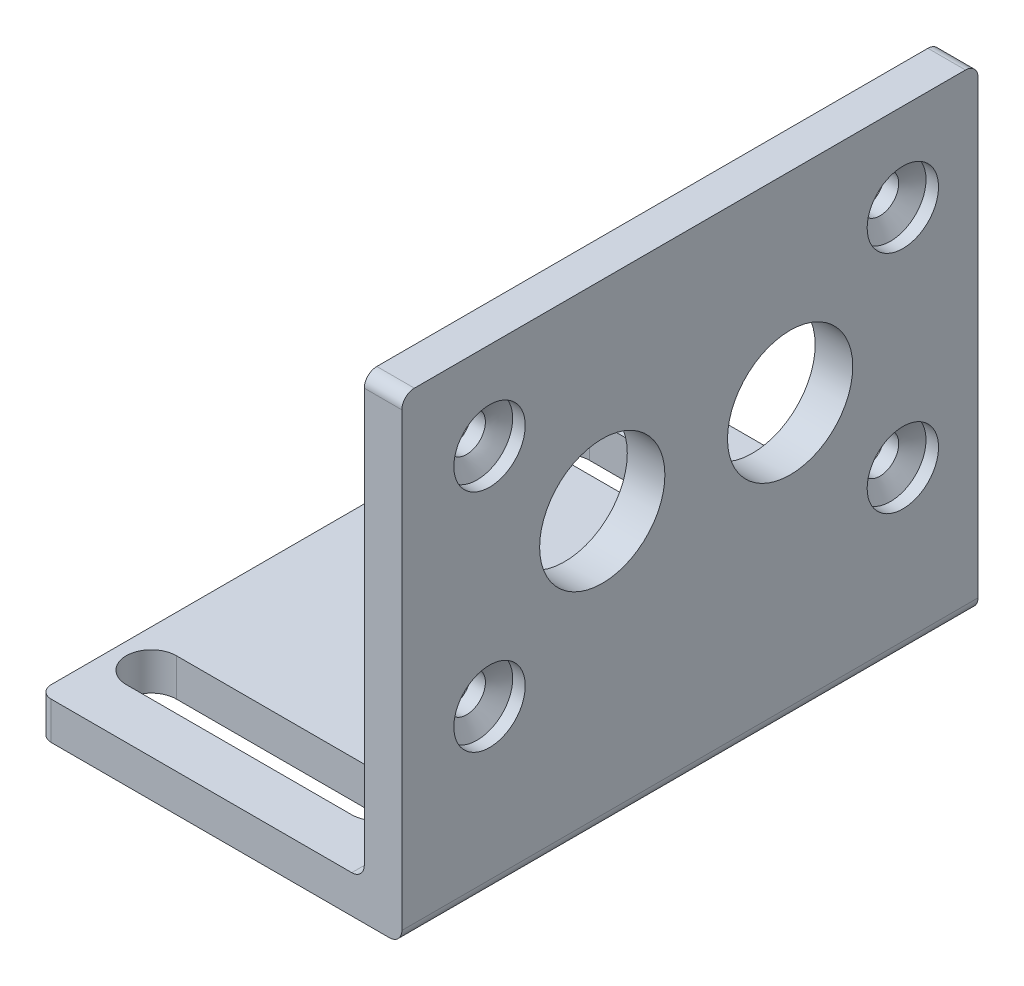
SolidWorks part; units mm, degrees
material "AISI 1020"
ref_plane "Alzado" through (0, 0, 0) normal (0, 0, 1) x (1, 0, 0)
ref_plane "Planta" through (0, 0, 0) normal (0, 1, 0) x (1, 0, 0)
ref_plane "Vista lateral" through (0, 0, 0) normal (1, 0, 0) x (0, 0, -1)
sketch "Croquis1" plane through (0, 0, 0) normal (0, 0, 1) x (1, 0, 0)
  line L0 (-36.9164, 3.6741) -> (-36.9164, -33.3259)
  line L1 (-37.9164, -34.3259) -> (-65.9164, -34.3259)
  line L2 (-65.9164, -34.3259) -> (-65.9164, -31.3259)
  line L3 (-65.9164, -31.3259) -> (-40.9164, -31.3259)
  line L4 (-39.9164, -30.3259) -> (-39.9164, 3.6741)
  line L5 (-39.9164, 3.6741) -> (-36.9164, 3.6741)
  arc A0 (-40.9164, -31.3259) -> (-39.9164, -30.3259) centre (-40.9164, -30.3259) ccw
  arc A1 (-36.9164, -33.3259) -> (-37.9164, -34.3259) centre (-37.9164, -33.3259) cw
  point P10 (-36.9164, -34.3259)
  dimension "D5" = 1
  dimension "D1" = 3
  dimension "D2" = 38
  dimension "D3" = 29
  dimension "D4" = 3
extrude "Saliente-Extruir1" add sketch "Croquis1" along normal blind 46
fillet "Redondeo1" radius 1 4 edges at (-38.4164, 3.6741, 0) (-65.9164, -32.8259, 0) (-65.9164, -32.8259, 46) (-38.4164, 3.6741, 46)
sketch "Croquis2" plane through (-36.9164, 0, 0) normal (-1, 0, 0) x (0, 0, 1)
  line L0 (1.9889, -7.7167) -> (5.3328, -7.7167) construction
  line L3 (0, 2.6741) -> (0, -30.3259) construction
  line L7 (45, 3.6741) -> (1, 3.6741) construction
  line L9 (1.9889, -7.7167) -> (1.9889, -13.0494) construction
  circle A0 centre (6, -3.3259) radius 2.85
  circle A1 centre (39, -3.3259) radius 2.85
  circle A2 centre (6, -21.3259) radius 2.85
  circle A3 centre (39, -21.3259) radius 2.85
  circle A4 centre (15, -12.3259) radius 5
  circle A5 centre (30, -12.3259) radius 5
  point P15 (5.1972, -7.3233)
  point P16 (2.0868, -13.0494)
  point P19 (6.8938, -7.5354)
  point P20 (41.8684, -7.435)
  point P21 (40.4468, -7.8666)
  point P24 (5.3328, -7.7167)
  dimension "D1" = 5.7
  dimension "D10" = 10
  dimension "D7" = 10
  dimension "D2" = 33
  dimension "D3" = 18
  dimension "D4" = 33
  dimension "D5" = 9
  dimension "D6" = 9
  dimension "D8" = 18
  dimension "D9" = 9
  dimension "D11" = 7
  dimension "D12" = 6
  dimension "D13" = 9
extrude "Cortar-Extruir1" cut sketch "Croquis2" along normal blind 1
sketch "Croquis3" plane through (0, -31.3259, 0) normal (0, 1, 0) x (1, 0, 0)
  line L0 (-62.9164, -42) -> (-44.9164, -42)
  line L1 (-62.9164, -38) -> (-44.9164, -38)
  line L3 (-40.9164, -46) -> (-64.9164, -46) construction
  line L4 (-73.4874, -23.5) -> (-32.2623, -23.5) construction
  line L5 (-62.9164, -9) -> (-44.9164, -9)
  line L6 (-62.9164, -5) -> (-44.9164, -5)
  arc A0 (-62.9164, -42) -> (-62.9164, -38) centre (-62.9164, -40) cw
  arc A1 (-44.9164, -38) -> (-44.9164, -42) centre (-44.9164, -40) cw
  arc A2 (-44.9164, -9) -> (-44.9164, -5) centre (-44.9164, -7) ccw
  arc A3 (-62.9164, -5) -> (-62.9164, -9) centre (-62.9164, -7) ccw
  point P6 (-53.9164, -42)
  dimension "D2" = 2
  dimension "D1" = 18
  dimension "D3" = 4
  dimension "D4" = 16.5
  dimension "D5" = 13
extrude "Cortar-Extruir2" cut sketch "Croquis3" against normal through all
ref_plane "Plano1" through (-38.7464, 0, 0) normal (1, 0, 0) x (0, 0, -1)
sketch "Croquis6" plane through (-36.9164, 0, 0) normal (1, 0, 0) x (0, 0, -1)
  circle A0 centre (-30, -12.3259) radius 5
  circle A1 centre (-15, -12.3259) radius 5
  dimension "D1" = 10
extrude "Cortar-Extruir3" cut sketch "Croquis6" against normal through all
sketch "Croquis7" plane through (-38.7464, 0, 0) normal (1, 0, 0) x (0, 0, -1)
  circle A0 centre (-39, -3.3259) radius 1.5
  circle A1 centre (-39, -21.3259) radius 1.5
  circle A2 centre (-6, -21.3259) radius 1.5
  circle A3 centre (-6, -3.3259) radius 1.5
  dimension "D1" = 3
loft "Cortar-Recubrir1" cut section edge at (-37.9164, -3.3259, 41.85) section "Croquis7" start constraint default connector at (-37.9164, -6.0715, 38.2359) connector at (-38.7464, -4.801, 39.2718)
loft "Cortar-Recubrir2" cut section edge at (-37.9164, -21.3259, 41.85) section "Croquis7<3>" connector at (-37.9164, -24.1759, 38.9964) connector at (-38.7464, -22.8259, 39.0033)
sketch "Croquis7<3>" plane through (-38.7464, 0, 0) normal (1, 0, 0) x (0, 0, -1) same geometry as "Croquis7"
loft "Cortar-Recubrir3" cut section edge at (-37.9164, -21.3259, 8.85) section "Croquis7<4>" connector at (-37.9164, -24.0509, 6.8346) connector at (-38.7464, -22.6435, 6.7168)
sketch "Croquis7<4>" plane through (-38.7464, 0, 0) normal (1, 0, 0) x (0, 0, -1) same geometry as "Croquis7"
loft "Cortar-Recubrir4" cut section edge at (-37.9164, -3.3259, 8.85) section "Croquis7<5>" connector at (-37.9164, -6.0199, 6.9299) connector at (-38.7464, -4.643, 6.7177)
sketch "Croquis7<5>" plane through (-38.7464, 0, 0) normal (1, 0, 0) x (0, 0, -1) same geometry as "Croquis7"
extrude "Cortar-Extruir4" cut sketch "Croquis7<6>" against normal through all
sketch "Croquis7<6>" plane through (-38.7464, 0, 0) normal (1, 0, 0) x (0, 0, -1) same geometry as "Croquis7"
